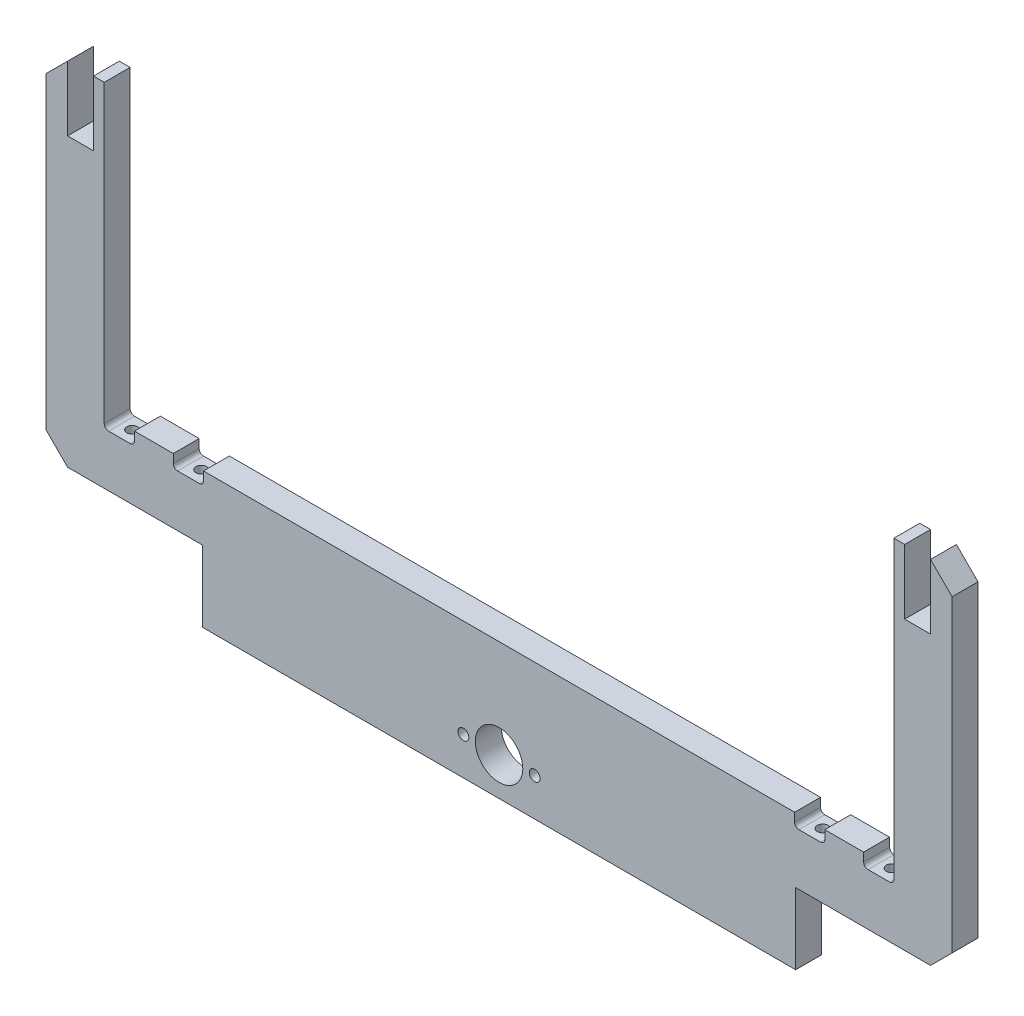
SolidWorks part; units mm, degrees
other "DetailItem1"
other "DetailItem2"
material "Beech"
ref_plane "Front Plane" through (0, 0, 0) normal (0, 0, 1) x (1, 0, 0)
ref_plane "Top Plane" through (0, 0, 0) normal (0, 1, 0) x (1, 0, 0)
ref_plane "Right Plane" through (0, 0, 0) normal (1, 0, 0) x (0, 0, -1)
sketch "Sketch1" plane through (0, 0, 0) normal (0, 0, 1) x (1, 0, 0)
  line L1 (-137.5, -16.5) -> (137.5, -16.5)
  line L2 (-137.5, -16.5) -> (-137.5, 16.5)
  line L3 (-137.5, 16.5) -> (137.5, 16.5)
  line L4 (137.5, -16.5) -> (137.5, 16.5)
  line L5 (-137.5, -16.5) -> (137.5, 16.5) construction
  line L6 (-137.5, 16.5) -> (137.5, -16.5) construction
  point P0 (0, 0)
  dimension "D1" = 275
  dimension "D2" = 33
extrude "Boss-Extrude1" add sketch "Sketch1" along normal blind 12
sketch "Sketch2" plane through (0, 0, 12) normal (0, 0, 1) x (1, 0, 0)
  line L0 (137.5, 16.5) -> (-137.5, 16.5) construction
  line L1 (-16.5, 1) -> (20.0379, 1) construction
  circle A0 centre (0, 1) radius 11
  circle A1 centre (-16.5, 1) radius 2.5
  circle A2 centre (16.5, 1) radius 2.5
  point P2 (0, 16.5)
  dimension "D1" = 15.5
  dimension "D2" = 22
  dimension "D3" = 5
  dimension "D4" = 5
  dimension "D5" = 33
  dimension "D6" = 16.5
extrude "Cut-Extrude1" cut sketch "Sketch2" against normal up to next
sketch "Sketch3" plane through (0, 0, 12) normal (0, 0, 1) x (1, 0, 0)
  line L1 (-210, 16.5) -> (210, 16.5)
  line L2 (-210, 16.5) -> (-210, 179.5)
  line L3 (-183, 46.5) -> (183, 46.5)
  line L4 (210, 16.5) -> (210, 179.5)
  line L5 (-210, 179.5) -> (-183, 179.5)
  line L8 (-183, 46.5) -> (-183, 179.5)
  line L9 (183, 179.5) -> (210, 179.5)
  line L13 (183, 46.5) -> (183, 179.5)
  circle A0 centre (0, 1) radius 11 construction
  dimension "D1" = 30
  dimension "D3" = 210
  dimension "D8" = 133
extrude "Boss-Extrude2" add sketch "Sketch3" against normal blind 12
sketch "Sketch4" plane through (0, 46.5, 0) normal (0, 1, 0) x (1, 0, 0)
  line L0 (-183, -6) -> (183, -6) construction
  line L1 (-183, 0) -> (-183, -12) construction
  line L2 (183, 0) -> (183, -12) construction
  line L4 (183, 0) -> (-183, 0) construction
  circle A0 centre (-144, -6) radius 2.5
  circle A1 centre (-176, -6) radius 2.5
  point P10 (0, 0)
  point P12 (0, 0)
  dimension "D1" = 5
  dimension "D2" = 5
  dimension "D3" = 144
  dimension "D4" = 176
extrude "Cut-Extrude2" cut sketch "Sketch4" against normal up to next
mirror "Mirror1" about plane through (0, 0, 0) normal (1, 0, 0) of "Cut-Extrude2"
sketch "Sketch5" plane through (0, 0, 12) normal (0, 0, 1) x (1, 0, 0)
  line L0 (-183, 46.5) -> (-183, 40.5)
  line L1 (-183, 40.5) -> (-169, 40.5)
  line L2 (-169, 40.5) -> (-169, 46.5)
  line L3 (183, 46.5) -> (-183, 46.5) construction
  line L4 (-169, 46.5) -> (-183, 46.5)
  line L5 (-151, 46.5) -> (-151, 40.5)
  line L6 (-151, 40.5) -> (-137, 40.5)
  line L7 (-137, 40.5) -> (-137, 46.5)
  line L8 (-151, 46.5) -> (-137, 46.5)
  circle A0 centre (0, 1) radius 11 construction
  dimension "D1" = 14
  dimension "D2" = 6
  dimension "D3" = 6
  dimension "D4" = 14
  dimension "D5" = 137
  dimension "D6" = 169
extrude "Cut-Extrude3" cut sketch "Sketch5" against normal up to next
fillet "Fillet1" radius 2 4 edges at (-137, 40.5, 6) (-151, 40.5, 6) (-169, 40.5, 6) (-183, 40.5, 6)
mirror "Mirror2" about plane through (0, 0, 0) normal (1, 0, 0) of "Fillet1", "Cut-Extrude3"
chamfer "Chamfer1" distance 10 angle 45 2 edges at (210, 16.5, 6) (-210, 16.5, 6)
sketch "Sketch6" plane through (0, 0, 12) normal (0, 0, 1) x (1, 0, 0)
  line L0 (-183, 179.5) -> (-210, 179.5) construction
  line L1 (-200, 179.5) -> (-188, 179.5)
  line L2 (-200, 179.5) -> (-200, 149.5)
  line L3 (-200, 149.5) -> (-188, 149.5)
  line L4 (-188, 179.5) -> (-188, 149.5)
  line L5 (-210, 179.5) -> (-210, 26.5) construction
  dimension "D1" = 12
  dimension "D2" = 10
  dimension "D3" = 30
extrude "Cut-Extrude4" cut sketch "Sketch6" against normal up to next
mirror "Mirror3" about plane through (0, 0, 0) normal (1, 0, 0) of "Cut-Extrude4"
chamfer "Chamfer2" distance 10 angle 45 2 edges at (210, 179.5, 6) (-210, 179.5, 6)
